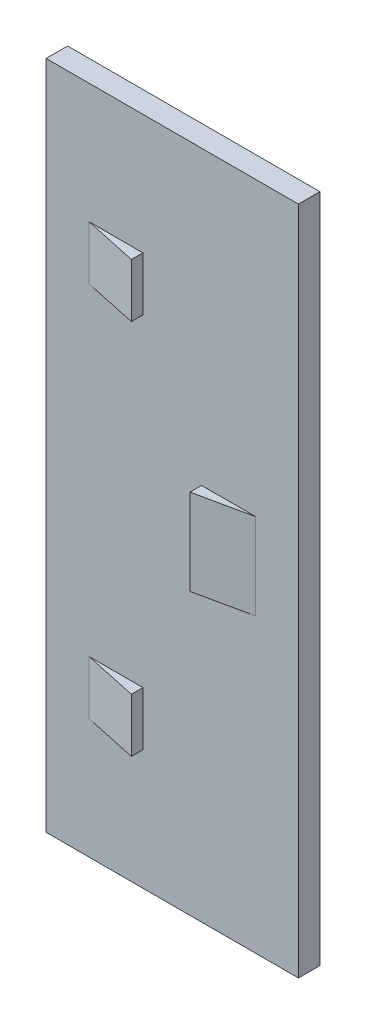
SolidWorks part; units mm, degrees
ref_plane "Спереди" through (0, 0, 0) normal (0, 0, 1) x (1, 0, 0)
ref_plane "Сверху" through (0, 0, 0) normal (0, 1, 0) x (1, 0, 0)
ref_plane "Справа" through (0, 0, 0) normal (1, 0, 0) x (0, 0, -1)
sketch "Эскиз1" plane through (0, 0, 0) normal (0, 0, 1) x (1, 0, 0)
  line L0 (51.456, -1504.6595) -> (39.256, -1504.6595) construction
  line L1 (0.28, -1501.6595) -> (-23.17, -1501.6595)
  line L2 (0.28, -1501.6595) -> (0.28, -1563.9595)
  line L3 (0.28, -1563.9595) -> (-23.17, -1563.9595)
  line L4 (-23.17, -1501.6595) -> (-23.17, -1563.9595)
  line L7 (-21.17, -1593.1774) -> (-21.17, -1576.9274) construction
  dimension "D1" = 2
  dimension "D2" = 23.45
  dimension "D3" = 62.3
  dimension "D4" = 3
extrude "Бобышка-Вытянуть1" add sketch "Эскиз1" along normal blind 2
sketch "Эскиз2" plane through (0, 0, 2) normal (0, 0, 1) x (1, 0, 0)
  line L0 (-23.17, -1532.8095) -> (0.28, -1532.8095) construction
  line L1 (-23.17, -1501.6595) -> (-23.17, -1563.9595) construction
  line L2 (0.28, -1563.9595) -> (0.28, -1501.6595) construction
  line L4 (-19.17, -1552.8095) -> (-14.17, -1552.8095)
  line L5 (-19.17, -1552.8095) -> (-19.17, -1547.8095)
  line L6 (-19.17, -1547.8095) -> (-14.17, -1547.8095)
  line L7 (-14.17, -1552.8095) -> (-14.17, -1547.8095)
  line L9 (-3.72, -1536.8095) -> (-8.72, -1536.8095)
  line L10 (-3.72, -1536.8095) -> (-3.72, -1528.8095)
  line L11 (-3.72, -1528.8095) -> (-8.72, -1528.8095)
  line L12 (-8.72, -1536.8095) -> (-8.72, -1528.8095)
  line L13 (-19.17, -1517.8095) -> (-14.17, -1517.8095)
  line L14 (-19.17, -1517.8095) -> (-19.17, -1512.8095)
  line L15 (-19.17, -1512.8095) -> (-14.17, -1512.8095)
  line L16 (-14.17, -1517.8095) -> (-14.17, -1512.8095)
  point P18 (-3.72, -1532.8095)
  dimension "D1" = 5
  dimension "D2" = 5
  dimension "D3" = 4
  dimension "D4" = 4
  dimension "D5" = 8
  dimension "D6" = 15
  dimension "D7" = 15
extrude "Бобышка-Вытянуть2" add sketch "Эскиз2" along normal blind 1.5
ref_plane "Плоскость1" through (0, -1532.8095, 0) normal (0, -1, 0) x (-1, 0, 0)
chamfer "Фаска1" distance 1.5 distance2 7 3 edges at (-19.17, -1515.3095, 3.5) (-3.72, -1532.8095, 3.5) (-19.17, -1550.3095, 3.5) first distance on face at (-19.17, -1515.3095, 2.75) first distance on face at (-3.72, -1532.8095, 2.75) first distance on face at (-19.17, -1550.3095, 2.75)
